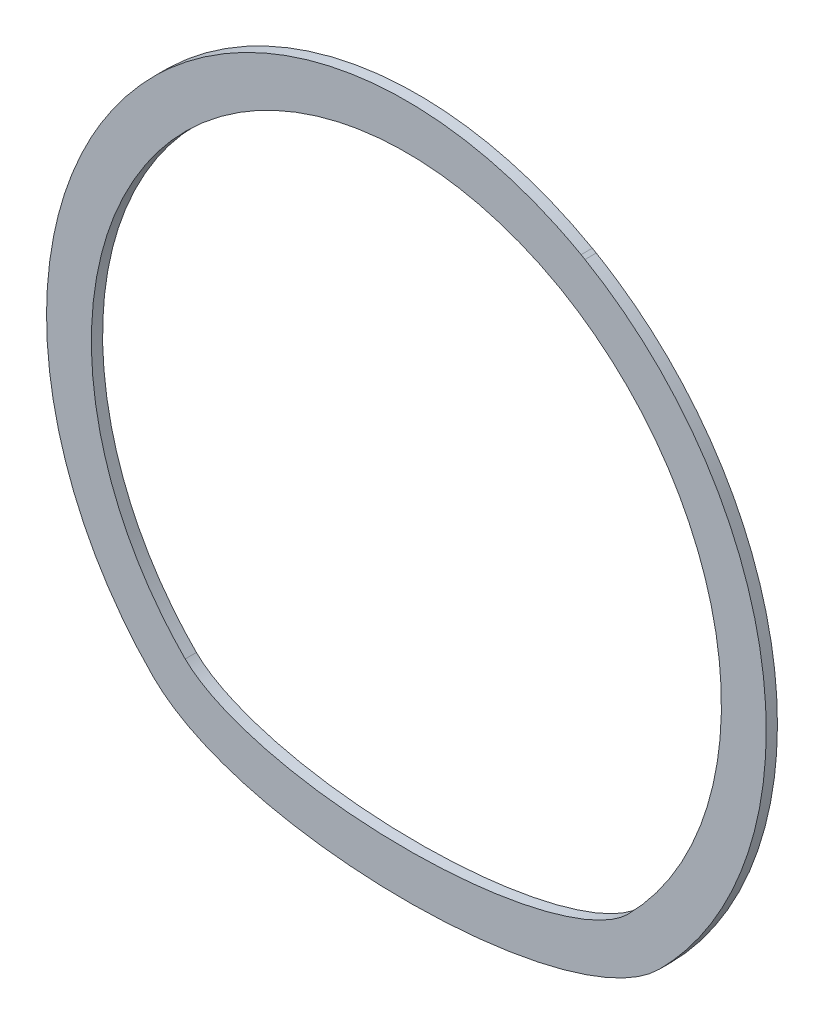
SolidWorks part; units mm, degrees
material "Balsa"
ref_plane "Front Plane" through (0, 0, 0) normal (0, 0, 1) x (1, 0, 0)
ref_plane "Top Plane" through (0, 0, 0) normal (0, 1, 0) x (1, 0, 0)
ref_plane "Right Plane" through (0, 0, 0) normal (1, 0, 0) x (0, 0, -1)
sketch "Sketch2" plane through (0, 0, 0) normal (0, 0, 1) x (1, 0, 0)
  spline S0 degree 3 poles (2568.0953, -4090.4659) (-4057.024, 3451.1389) (4945.1528, -1980.2124) (-4825.8731, 402.3844) knots -545.10296 -545.10296 -545.10296 -545.10296 547.49362 547.49362 547.49362 547.49362 only from (49.5009, 91.348) to (50.6103, 90.7129)
  spline S1 degree 3 poles (3341.4723, -3725.6669) (-100.6677, -22.1088) (-50.1916, -95.8099) (-74.4696, -70.0026) (-75.8372, -68.488) (-77.1861, -66.9319) (-78.5157, -65.3347) (-79.8244, -63.6962) (-81.5476, -61.4464) (-83.6416, -58.5297) (-85.6296, -55.5014) (-87.1622, -52.9973) (-88.2859, -51.0701) (-90.1147, -47.7724) (-92.5499, -42.8914) (-95.3516, -36.1752) (-97.8068, -28.8548) (-99.4166, -22.4927) (-100.4844, -16.9735) (-101.2174, -12.1158) (-101.8059, -6.1085) (-102.0556, 1.0556) (-101.6376, 11.9166) (-99.5817, 24.7034) (-94.9478, 39.4776) (-88.6565, 52.7081) (-80.0434, 65.5541) (-69.8712, 76.7554) (-58.637, 85.9148) (-47.202, 92.899) (-35.7905, 98.0522) (-24.0008, 101.7167) (-12.0295, 103.8942) (-3.6569, 104.3953) (0.9911, 104.3723) (2.6447, 104.3478) (5.2959, 104.2559) (8.9441, 104.0024) (12.9235, 103.5662) (16.8979, 102.9692) (20.8607, 102.2106) (24.805, 101.2899) (28.7242, 100.207) (32.6113, 98.9619) (36.4593, 97.5551) (39.9429, 96.1186) (42.4433, 94.9816) (43.9946, 94.2376) (44.9225, 93.7809) (45.8466, 93.3143) (46.7667, 92.8378) (47.6827, 92.3514) (70.4007, 80.003) (151.5153, 23.3747) (-4363.3748, 2440.7113) knots -0.313173 -0.313173 -0.313173 -0.313173 0.006795 0.013654 0.020575 0.02756 0.034609 0.041722 0.048899 0.063446 0.078252 0.085753 0.09332 0.100952 0.124124 0.148785 0.174948 0.202627 0.215494 0.232144 0.2526 0.276886 0.305032 0.363116 0.408011 0.462235 0.511576 0.564908 0.615598 0.658549 0.700916 0.742691 0.78387 0.82445 0.827809 0.831171 0.841279 0.854802 0.868378 0.882008 0.895692 0.909428 0.923217 0.93706 0.950955 0.964902 0.975398 0.978902 0.982411 0.985922 0.989437 0.992954 0.996476 1.262403 1.262403 1.262403 1.262403 only from (-71.6774, -72.9104) to (49.5009, 91.348)
  spline S2 degree 3 poles (-71.6774, -72.9104) (-72.1092, -72.4767) (-72.9729, -71.5936) (-74.4696, -70.0026) (-75.8372, -68.488) (-77.1861, -66.9319) (-78.5157, -65.3347) (-79.8244, -63.6962) (-81.5476, -61.4464) (-83.6416, -58.5297) (-85.6296, -55.5014) (-87.1622, -52.9973) (-88.2859, -51.0701) (-90.1147, -47.7724) (-92.5499, -42.8914) (-95.3516, -36.1752) (-97.8068, -28.8548) (-99.4166, -22.4927) (-100.4844, -16.9735) (-101.2174, -12.1158) (-101.8059, -6.1085) (-102.0556, 1.0556) (-101.6376, 11.9166) (-99.5817, 24.7034) (-94.9478, 39.4776) (-88.6565, 52.7081) (-80.0434, 65.5541) (-69.8712, 76.7554) (-58.637, 85.9148) (-47.202, 92.899) (-35.7905, 98.0522) (-24.0008, 101.7167) (-12.0295, 103.8942) (-3.6569, 104.3953) (0.9911, 104.3723) (2.6447, 104.3478) (5.2959, 104.2559) (8.9441, 104.0024) (12.9235, 103.5662) (16.8979, 102.9692) (20.8607, 102.2106) (24.805, 101.2899) (28.7242, 100.207) (32.6113, 98.9619) (36.4593, 97.5551) (39.9429, 96.1186) (42.4433, 94.9816) (43.9946, 94.2376) (44.9225, 93.7809) (45.8466, 93.3143) (46.7667, 92.8378) (47.6827, 92.3514) (48.5618, 91.8735) (49.1883, 91.5244) (49.5009, 91.348) knots 0 0 0 0 0.006795 0.013654 0.020575 0.02756 0.034609 0.041722 0.048899 0.063446 0.078252 0.085753 0.09332 0.100952 0.124124 0.148785 0.174948 0.202627 0.215494 0.232144 0.2526 0.276886 0.305032 0.363116 0.408011 0.462235 0.511576 0.564908 0.615598 0.658549 0.700916 0.742691 0.78387 0.82445 0.827809 0.831171 0.841279 0.854802 0.868378 0.882008 0.895692 0.909428 0.923217 0.93706 0.950955 0.964902 0.975398 0.978902 0.982411 0.985922 0.989437 0.992954 0.996476 1 1 1 1
  spline S3 degree 3 poles (49.5009, 91.348) (49.872, 91.1385) (50.2418, 90.9268) (50.6103, 90.7129) knots 0 0 0 0 1 1 1 1
  spline S4 degree 3 poles (-4193.7763, 2732.8048) (81.5381, 53.7028) (23.1515, 107.7521) (53.9325, 88.7036) (55.5798, 87.6387) (57.2181, 86.5331) (58.847, 85.3874) (60.4652, 84.2011) (62.6149, 82.559) (65.2687, 80.4032) (68.3802, 77.661) (71.4204, 74.7537) (74.3792, 71.6812) (77.2464, 68.4441) (79.5428, 65.6199) (81.3243, 63.2803) (82.6352, 61.4798) (83.9151, 59.6395) (85.6826, 56.9767) (87.8969, 53.3695) (90.4626, 48.6769) (92.8892, 43.6261) (95.1327, 38.2157) (97.1465, 32.4482) (98.8821, 26.3306) (100.2892, 19.8751) (101.2586, 13.4739) (101.8173, 7.2467) (102.0152, 1.305) (101.8786, -4.6242) (101.3926, -10.7347) (100.5371, -16.8676) (99.3294, -22.8638) (97.8936, -28.3722) (96.657, -32.2698) (95.7856, -34.7444) (95.046, -36.7643) (93.9532, -39.5358) (92.4358, -43.007) (90.8217, -46.3649) (89.1186, -49.6082) (87.3342, -52.7363) (85.4757, -55.7486) (83.5505, -58.6453) (81.5655, -61.4266) (79.3077, -64.3807) (77.437, -66.6472) (76.0073, -68.2889) (75.2951, -69.0897) (74.579, -69.8782) (73.8594, -70.6545) (73.1363, -71.4184) (59.0939, -85.9325) (120.7935, -16.6257) (-3396.6628, -3673.2191) knots -0.504739 -0.504739 -0.504739 -0.504739 0.010157 0.020393 0.030709 0.041103 0.051576 0.062128 0.072758 0.094254 0.116062 0.138181 0.16061 0.183347 0.206391 0.218027 0.22974 0.241529 0.253393 0.280162 0.30828 0.337739 0.36853 0.400644 0.434071 0.4688 0.504821 0.536145 0.567394 0.59857 0.62967 0.664059 0.696204 0.726123 0.75383 0.760691 0.767516 0.787768 0.807688 0.827278 0.84654 0.865477 0.884089 0.902378 0.920346 0.937994 0.961032 0.966703 0.97234 0.977942 0.983508 0.98904 0.994538 1.266327 1.266327 1.266327 1.266327 only from (50.6103, 90.7129) to (71.6784, -72.9104)
  spline S5 degree 3 poles (50.6103, 90.7129) (51.1284, 90.4118) (52.1672, 89.796) (53.9325, 88.7036) (55.5798, 87.6387) (57.2181, 86.5331) (58.847, 85.3874) (60.4652, 84.2011) (62.6149, 82.559) (65.2687, 80.4032) (68.3802, 77.661) (71.4204, 74.7537) (74.3792, 71.6812) (77.2464, 68.4441) (79.5428, 65.6199) (81.3243, 63.2803) (82.6352, 61.4798) (83.9151, 59.6395) (85.6826, 56.9767) (87.8969, 53.3695) (90.4626, 48.6769) (92.8892, 43.6261) (95.1327, 38.2157) (97.1465, 32.4482) (98.8821, 26.3306) (100.2892, 19.8751) (101.2586, 13.4739) (101.8173, 7.2467) (102.0152, 1.305) (101.8786, -4.6242) (101.3926, -10.7347) (100.5371, -16.8676) (99.3294, -22.8638) (97.8936, -28.3722) (96.657, -32.2698) (95.7856, -34.7444) (95.046, -36.7643) (93.9532, -39.5358) (92.4358, -43.007) (90.8217, -46.3649) (89.1186, -49.6082) (87.3342, -52.7363) (85.4757, -55.7486) (83.5505, -58.6453) (81.5655, -61.4266) (79.3077, -64.3807) (77.437, -66.6472) (76.0073, -68.2889) (75.2951, -69.0897) (74.579, -69.8782) (73.8594, -70.6545) (73.1363, -71.4184) (72.3175, -72.2647) (71.8912, -72.6967) (71.6784, -72.9104) knots 0 0 0 0 0.010157 0.020393 0.030709 0.041103 0.051576 0.062128 0.072758 0.094254 0.116062 0.138181 0.16061 0.183347 0.206391 0.218027 0.22974 0.241529 0.253393 0.280162 0.30828 0.337739 0.36853 0.400644 0.434071 0.4688 0.504821 0.536145 0.567394 0.59857 0.62967 0.664059 0.696204 0.726123 0.75383 0.760691 0.767516 0.787768 0.807688 0.827278 0.84654 0.865477 0.884089 0.902378 0.920346 0.937994 0.961032 0.966703 0.97234 0.977942 0.983508 0.98904 0.994538 1 1 1 1
  spline S6 degree 3 poles (-4835.9061, 806.008) (5645.7753, -391.3089) (-5645.7177, -391.3145) (4835.7602, 805.9912) knots -2.930767 -2.930767 -2.930767 -2.930767 3.930735 3.930735 3.930735 3.930735 weights 1 1 1 1 only from (71.6784, -72.9104) to (-71.6774, -72.9104)
  spline S7 degree 3 poles (71.6784, -72.9104) (46.3599, -98.3417) (-46.3589, -98.3417) (-71.6774, -72.9104) knots 0 0 0 0 1 1 1 1 weights 1 1 1 1
  spline S8 degree 1 poles (-62.6772, -63.9502) (43.2582, 80.2883) knots 0 0 1 1 construction
  spline S9 degree 1 poles (43.2582, 80.2883) (44.2327, 79.7303) knots 0 0 1 1 construction
  spline S10 degree 1 poles (44.2327, 79.7303) (62.6782, -63.9502) knots 0 0 1 1 construction
  spline S11 degree 1 poles (62.6782, -63.9502) (-62.6772, -63.9502) knots 0 0 1 1 construction
  spline S12 degree 3 poles (-62.6772, -63.9502) (-62.8955, -63.7309) (-63.3217, -63.2983) (-64.0021, -62.5921) (-64.7538, -61.7946) (-65.7039, -60.7646) (-66.8046, -59.5274) (-68.5568, -57.4681) (-70.6482, -54.8355) (-73.8114, -50.469) (-77.3945, -44.7561) (-82.3029, -35.1354) (-86.8108, -22.36) (-90.3543, -0.9674) (-87.6499, 26.3501) (-73.3334, 55.9721) (-49.624, 78.7088) (-24.4872, 89.3835) (-3.091, 92.1159) (13.039, 91.1975) (26.1203, 87.9966) (34.8794, 84.5248) (39.1021, 82.5104) (41.2143, 81.4108) (42.347, 80.7976) (42.9592, 80.4569) (43.2582, 80.2883) knots 0 0 0 0 0.003906 0.007812 0.011719 0.015625 0.023437 0.03125 0.046875 0.062499 0.093749 0.124999 0.187498 0.249998 0.374997 0.499996 0.624995 0.749994 0.812493 0.874993 0.937492 0.968742 0.984367 0.992179 0.996085 0.999992 0.999992 0.999992 0.999992
  spline S13 degree 3 poles (43.2582, 80.2883) (43.3397, 80.2423) (43.5025, 80.15) (43.7464, 80.0108) (43.9898, 79.871) (44.1518, 79.7773) (44.2327, 79.7303) knots 0.002022 0.002022 0.002022 0.002022 0.251014 0.500005 0.748996 0.997987 0.997987 0.997987 0.997987
  spline S14 degree 3 poles (44.2327, 79.7303) (44.5844, 79.526) (45.2596, 79.1276) (46.4154, 78.4223) (47.5738, 77.6928) (49.0079, 76.7584) (50.8048, 75.5306) (53.6072, 73.4932) (57.0034, 70.7903) (64.7641, 63.8421) (74.8536, 51.7693) (84.3118, 33.0007) (89.3026, 12.5818) (89.5941, -8.4639) (85.1673, -29.0225) (78.4712, -43.2887) (72.7378, -52.0045) (70.1455, -55.4923) (67.9548, -58.1887) (66.5372, -59.8344) (65.3768, -61.1241) (64.6361, -61.9238) (64.0489, -62.544) (63.5408, -63.0721) (63.0657, -63.5594) (62.8132, -63.8146) (62.6782, -63.9502) knots 0.000015 0.000015 0.000015 0.000015 0.007827 0.015639 0.023452 0.031264 0.046889 0.062514 0.093763 0.125013 0.250011 0.375009 0.500007 0.625005 0.750004 0.875002 0.906251 0.937501 0.953126 0.96875 0.976563 0.984375 0.988281 0.992188 0.996094 1 1 1 1
  spline S15 degree 3 poles (62.6782, -63.9502) (62.4421, -64.1873) (61.9735, -64.6322) (60.8483, -65.5949) (59.1789, -66.8259) (56.7375, -68.3252) (52.9423, -70.2888) (47.261, -72.5995) (39.2215, -74.978) (30.229, -76.8801) (17.3048, -78.7217) (0.0005, -79.6587) (-17.3038, -78.7217) (-30.228, -76.8801) (-39.2204, -74.978) (-47.2599, -72.5995) (-52.9413, -70.2888) (-56.7364, -68.3252) (-59.1779, -66.8259) (-60.8473, -65.5949) (-61.9724, -64.6322) (-62.4411, -64.1873) (-62.6772, -63.9502) knots 0 0 0 0 0.015625 0.03125 0.0625 0.09375 0.125 0.1875 0.25 0.3125 0.375 0.5 0.625 0.6875 0.75 0.8125 0.875 0.90625 0.9375 0.96875 0.984375 1 1 1 1
  dimension "D1" = 12.7
extrude "Boss-Extrude1" add sketch "Sketch2" against normal blind 3.175
